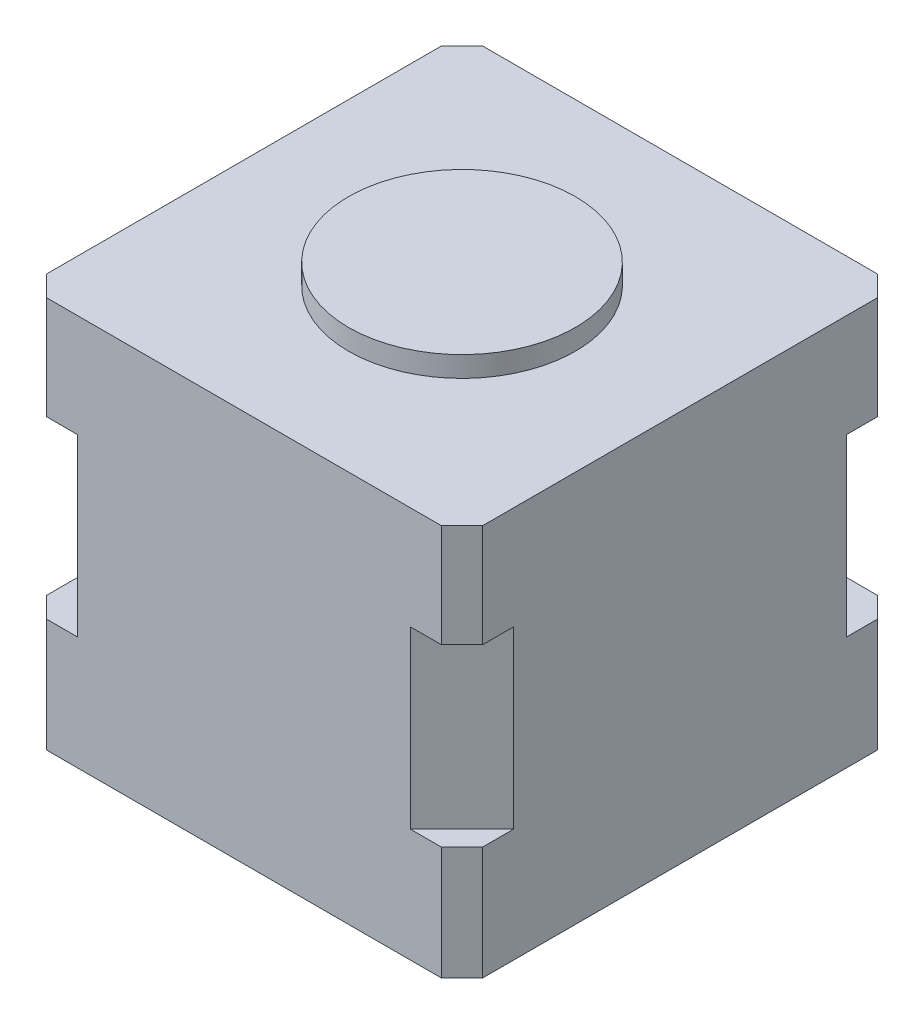
SolidWorks part; units mm, degrees
ref_plane "Front Plane" through (0, 0, 0) normal (0, 0, 1) x (1, 0, 0)
ref_plane "Top Plane" through (0, 0, 0) normal (0, 1, 0) x (1, 0, 0)
ref_plane "Right Plane" through (0, 0, 0) normal (1, 0, 0) x (0, 0, -1)
sketch "Sketch1" plane through (0, 0, 0) normal (0, 1, 0) x (1, 0, 0)
  line L0 (19.15, -21.15) -> (21.15, -19.15)
  line L1 (-19.15, 21.15) -> (19.15, 21.15)
  line L2 (-21.15, 19.15) -> (-21.15, -19.15)
  line L3 (-19.15, -21.15) -> (19.15, -21.15)
  line L4 (21.15, 19.15) -> (21.15, -19.15)
  line L5 (-21.15, 21.15) -> (21.15, -21.15) construction
  line L6 (-21.15, -21.15) -> (21.15, 21.15) construction
  line L7 (-21.15, -19.15) -> (-19.15, -21.15)
  line L8 (-21.15, 19.15) -> (-19.15, 21.15)
  line L9 (19.15, 21.15) -> (21.15, 19.15)
  point P0 (0, 0)
  dimension "D1" = 42.3
  dimension "D2" = 42.3
  dimension "D3" = 2
  dimension "D4" = 45
  dimension "D5" = 2
  dimension "D6" = 45
  dimension "D7" = 2
  dimension "D8" = 45
  dimension "D9" = 2
  dimension "D10" = 45
extrude "Boss-Extrude1" add sketch "Sketch1" along normal blind 11
sketch "Sketch2" plane through (0, 11, 0) normal (0, 1, 0) x (1, 0, 0)
  line L0 (16.15, -21.15) -> (21.15, -16.15)
  line L1 (-16.15, 21.15) -> (16.15, 21.15)
  line L2 (-21.15, 16.15) -> (-21.15, -16.15)
  line L3 (-16.15, -21.15) -> (16.15, -21.15)
  line L4 (21.15, 16.15) -> (21.15, -16.15)
  line L5 (-21.15, 21.15) -> (21.15, -21.15) construction
  line L6 (-21.15, -21.15) -> (21.15, 21.15) construction
  line L7 (-21.15, -16.15) -> (-16.15, -21.15)
  line L8 (16.15, 21.15) -> (21.15, 16.15)
  line L9 (-21.15, 16.15) -> (-16.15, 21.15)
  point P0 (0, 0)
  dimension "D1" = 42.3
  dimension "D2" = 42.3
extrude "Boss-Extrude2" add sketch "Sketch2" along normal blind 17
sketch "Sketch3" plane through (0, 28, 0) normal (0, 1, 0) x (1, 0, 0)
  line L0 (19.15, -21.15) -> (21.15, -19.15)
  line L1 (-19.15, 21.15) -> (19.15, 21.15)
  line L2 (-21.15, 19.15) -> (-21.15, -19.15)
  line L3 (-19.15, -21.15) -> (19.15, -21.15)
  line L4 (21.15, 19.15) -> (21.15, -19.15)
  line L5 (-21.15, 21.15) -> (21.15, -21.15) construction
  line L6 (-21.15, -21.15) -> (21.15, 21.15) construction
  line L7 (19.15, 21.15) -> (21.15, 19.15)
  line L8 (-21.15, 19.15) -> (-19.15, 21.15)
  line L9 (-21.15, -19.15) -> (-19.15, -21.15)
  point P0 (0, 0)
  dimension "D1" = 42.3
  dimension "D2" = 42.3
extrude "Boss-Extrude3" add sketch "Sketch3" along normal blind 10
sketch "Sketch4" plane through (0, 38, 0) normal (0, 1, 0) x (1, 0, 0)
  circle A0 centre (0, 0) radius 11
  dimension "D1" = 22
extrude "Boss-Extrude4" add sketch "Sketch4" along normal blind 2
sketch "Sketch8" plane through (0, 0, 0) normal (0, -1, 0) x (1, 0, 0)
  line L0 (-30.0282, 0) -> (31.49, 0) construction
  line L1 (0, 25.3918) -> (0, -26.839) construction
  circle A0 centre (-15.5, 15.5) radius 1.5
  circle A1 centre (15.5, 15.5) radius 1.5
  circle A2 centre (15.5, -15.5) radius 1.5
  circle A3 centre (-15.5, -15.5) radius 1.5
  point P13 (0, 0)
  point P14 (0, 0)
  point P15 (18.0375, 14.9569)
  dimension "D1" = 3
  dimension "D2" = 31
  dimension "D3" = 31
extrude "Cut-Extrude2" cut sketch "Sketch8" against normal blind 4.5
